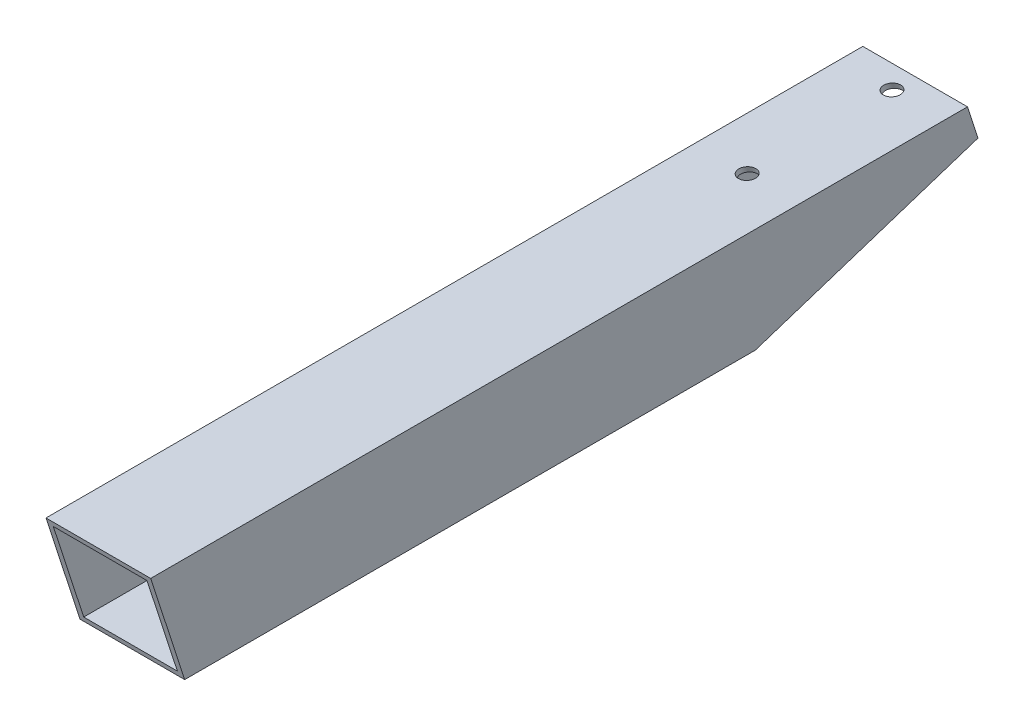
SolidWorks part; units mm, degrees
material "Gerais  - 6061-T6"
ref_plane "Plano frontal" through (0, 0, 0) normal (0, 0, 1) x (1, 0, 0)
ref_plane "Plano superior" through (0, 0, 0) normal (0, 1, 0) x (1, 0, 0)
ref_plane "Plano direito" through (0, 0, 0) normal (1, 0, 0) x (0, 0, -1)
sketch "Esboço1" plane through (0, 0, 0) normal (0, 0, 1) x (1, 0, 0)
  line L1 (-9.5, 9.5) -> (9.5, 9.5)
  line L2 (-9.5, 9.5) -> (-9.5, -9.5)
  line L3 (-9.5, -9.5) -> (9.5, -9.5)
  line L4 (9.5, 9.5) -> (9.5, -9.5)
  line L5 (-9.5, 9.5) -> (9.5, -9.5) construction
  line L6 (-9.5, -9.5) -> (9.5, 9.5) construction
  line L11 (-5.6574, 5.6574) -> (5.6574, -5.6574) construction
  line L12 (-5.6574, -5.6574) -> (5.6574, 5.6574) construction
  point P0 (0, 0)
  point P6 (0, 0)
  dimension "D1" = 19
extrude "Ressalto-extrusão1" add sketch "Esboço1" along normal blind 260
shell "Casca2" thickness 1 removed face at (0, 0, 0) removed face at (0, 0, 260)
sketch "Esboço2" plane through (9.5, 0, 0) normal (1, 0, 0) x (0, 0, -1)
  line L0 (0, 9.5) -> (-58.476, -9.5)
  line L1 (-260, -9.5) -> (0, -9.5) construction
  line L4 (-260, 9.5) -> (0, 9.5) construction
  line L5 (-58.476, -9.5) -> (0, -9.5)
  line L7 (0, -9.5) -> (0, 9.5)
  dimension "D1" = 18
extrude "Corte-extrusão1" cut sketch "Esboço2" against normal through all
sketch "Esboço4" plane through (9.5, 0, 0) normal (1, 0, 0) x (0, 0, -1)
  line L0 (-168.5503, 10.4737) -> (-161.2895, -11.8728)
  line L1 (-161.2895, -11.8728) -> (-264.8128, -45.5096)
  line L2 (-264.8128, -45.5096) -> (-289.0578, 22.1497)
  line L3 (-289.0578, 22.1497) -> (-184.5161, 59.6112)
  line L4 (-184.5161, 59.6112) -> (-168.5503, 10.4737)
extrude "Corte-extrusão3" cut sketch "Esboço4" against normal through all
sketch "Esboço5" plane through (0, 9.5, 0) normal (0, 0.9511, 0.309) x (1, 0, 0)
  line L0 (9.5, 0) -> (-9.5, 0) construction
  line L1 (9.5, -160) -> (-9.5, -160) construction
  circle A0 centre (0, -23) radius 1.5
  circle A1 centre (0, -48) radius 1.5
  point P4 (0, 0)
  point P8 (0, 0)
  dimension "D3" = 3
  dimension "D1" = 112
  dimension "D2" = 25
extrude "Corte-extrusão4" cut sketch "Esboço5" along normal through all
sketch "Esboço7" plane through (0, 8.5928, 2.792) normal (0, -0.9511, -0.309) x (1, 0, 0)
  line L0 (-9.5, -2.9357) -> (-9.5, 58.5496) construction
  line L1 (9.5, -2.9357) -> (-9.5, -2.9357)
  line L2 (9.5, -2.9357) -> (9.5, 16.0643)
  line L3 (9.5, 16.0643) -> (-9.5, 16.0643)
  line L4 (-9.5, -2.9357) -> (-9.5, 16.0643)
  ellipse E0 centre (0, 20.0643) end of major axis (1.5, 20.0643) minor radius 1.5 construction
  point P7 (0, 20.0643)
  point P8 (0, 0)
  point P14 (0, 18.0605)
  dimension "D1" = 4
extrude "Corte-extrusão6" cut sketch "Esboço7" against normal through all
